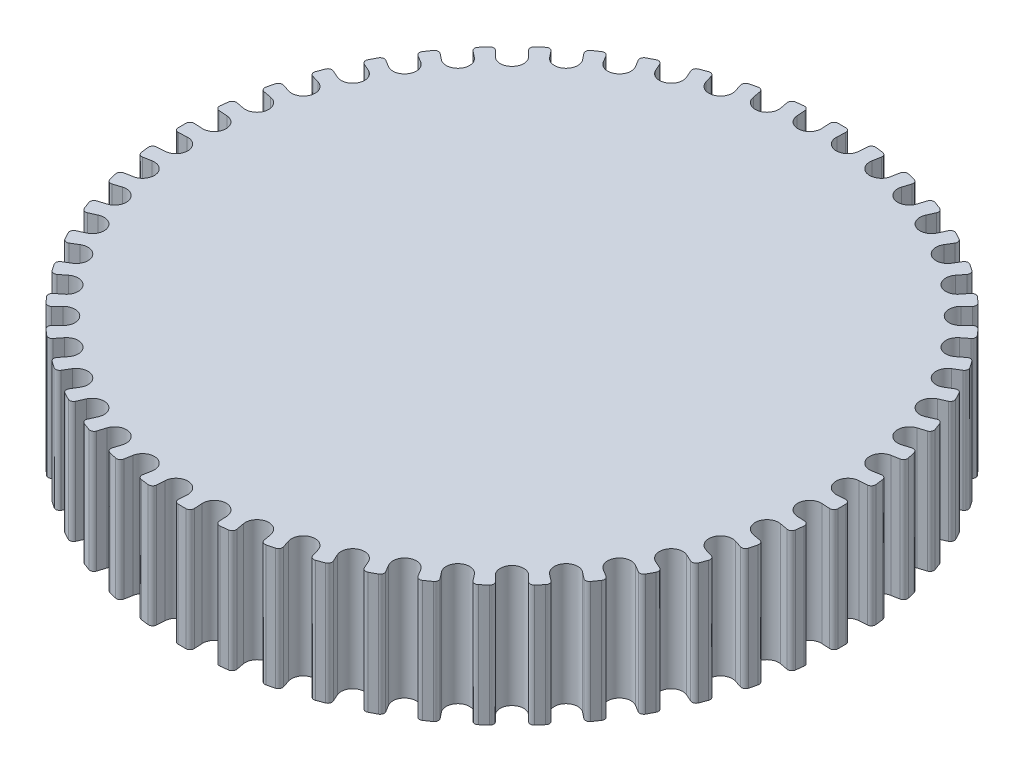
SolidWorks part; units mm, degrees
ref_plane "Front Plane" through (0, 0, 0) normal (0, 0, 1) x (1, 0, 0)
ref_plane "Top Plane" through (0, 0, 0) normal (0, 1, 0) x (1, 0, 0)
ref_plane "Right Plane" through (0, 0, 0) normal (1, 0, 0) x (0, 0, -1)
sketch "Sketch5" plane through (0, 0, 0) normal (0, 1, 0) x (1, 0, 0)
  line L0 (0, 0) -> (0, 41.3803) construction
  line L1 (0, 0) -> (-4.9878, 41.0786) construction
  line L2 (-3.908, 40.5926) -> (-3.816, 39.0712)
  line L3 (-1.0133, 40.7677) -> (-0.9213, 39.2463)
  line L4 (-4.9155, 40.483) -> (0, 40.7803) construction
  line L5 (-2.4578, 40.6316) -> (-2.3687, 39.1587) construction
  circle A0 centre (0, 0) radius 41.3803 construction
  circle A4 centre (0, 0) radius 40.7803
  circle A6 centre (0, 0) radius 37.7803 construction
  arc A7 (-3.816, 39.0712) -> (-0.9213, 39.2463) centre (-2.3687, 39.1587) ccw
  dimension "D1" = 82.7606
  dimension "D2" = 1.45
  dimension "D5" = 0.6
  dimension "D6" = 6.923
  dimension "D8" = 3
ref_axis "Axis1" through (0, 36.9714, 0) along (0, -1, 0)
extrude "Boss-Extrude1" add sketch "Sketch5" along normal mid plane 15 contours A7 L2 A4 L3 | L2 A7 L3 A4 region at (-2.3796, 0, -39.3401) region at (0.0035, 0, 0.0586)
extrude "Cut-Extrude1" cut sketch "Sketch5<3>" against normal through all and the other way through all contours L2 A7 L3 A4 region at (-2.3796, 0, -39.3401)
sketch "Sketch5<3>" plane through (0, 0, 0) normal (0, 1, 0) x (1, 0, 0) same geometry as "Sketch5"
fillet "Fillet1" radius 0.5 2 edges at (-3.908, 0, -40.5926) (-1.0133, 0, -40.7677)
pattern_circular "CirPattern1" count 52 over 360 about axis through (0, 36.9714, 0) along (0, -1, 0) of "Fillet1", "Cut-Extrude1"
equation "\"Pitch\"= 5mm"
equation "\"ToothNum\"= 52"
equation "\"Angle\"= 360deg / \"ToothNum\""
equation "\"PitchDiam\"= ( \"Pitch\" * \"ToothNum\" ) / pi"
equation "\"D1@Sketch5\"=\"PitchDiam\""
equation "\"D6@Sketch5\"=\"Angle\""
equation "\"GearHeight\" = 15"
equation "\"D1@Boss-Extrude1\"=\"GearHeight\""
equation "\"D1@Fillet1\"=\"Pitch\"/10"
equation "\"D1@CirPattern1\"=\"ToothNum\""
